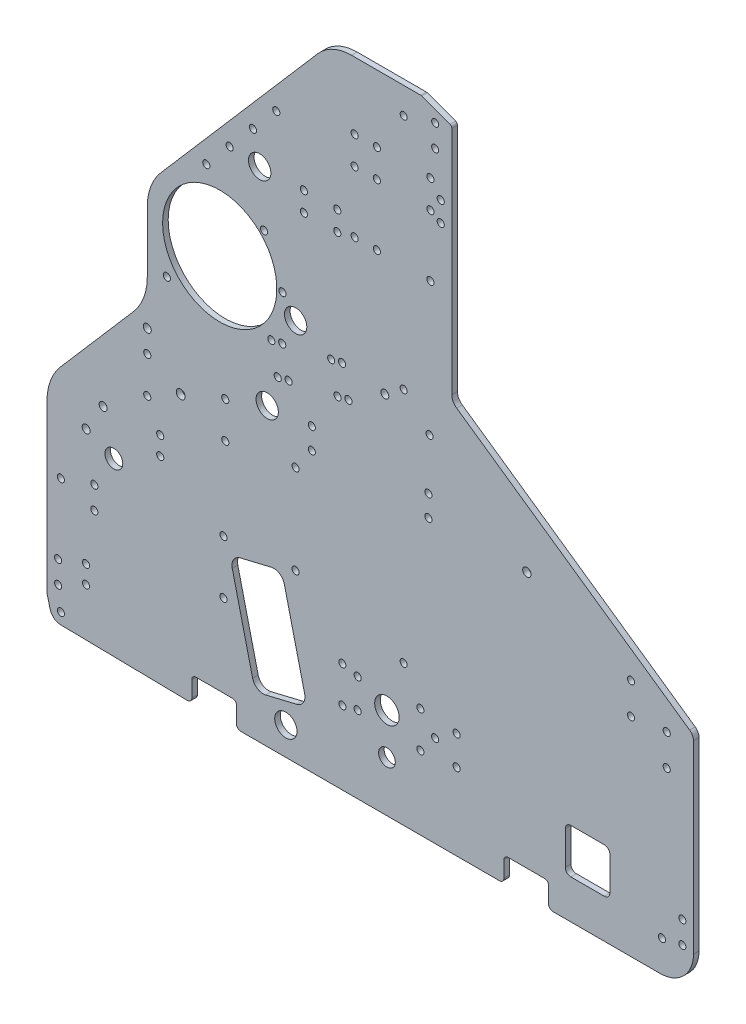
SolidWorks part; units mm, degrees
ref_plane "Front Plane" through (0, 0, 0) normal (0, 0, 1) x (1, 0, 0)
ref_plane "Top Plane" through (0, 0, 0) normal (0, 1, 0) x (1, 0, 0)
ref_plane "Right Plane" through (0, 0, 0) normal (1, 0, 0) x (0, 0, -1)
sketch "Sketch1" plane through (0, 0, 0) normal (0, 0, 1) x (1, 0, 0)
  line L0 (82.55, -20.32) -> (82.55, -6.35)
  line L2 (0, 0) -> (0, 157.48)
  line L4 (368.3, -20.32) -> (368.3, 106.68)
  line L5 (82.55, -6.35) -> (107.95, -6.35)
  line L6 (107.95, -6.35) -> (107.95, -20.32)
  line L7 (107.95, -20.32) -> (260.35, -20.32)
  line L8 (260.35, -20.32) -> (260.35, -6.35)
  line L9 (260.35, -6.35) -> (285.75, -6.35)
  line L10 (285.75, -6.35) -> (285.75, -20.32)
  line L11 (285.75, -20.32) -> (368.3, -20.32)
  line L12 (361.95, 12.7) -> (368.3, 12.7) construction
  line L13 (0, 0) -> (6.35, 0) construction
  line L14 (0.1896, -7.8901) -> (1.7771, -14.2401)
  line L15 (7.8295, -19.0491) -> (82.55, -20.32)
  line L16 (0, 0) -> (0, -6.35)
  line L17 (76.2, 128.905) -> (79.375, 128.905) construction
  line L18 (57.15, 118.5863) -> (101.6, 118.5862) construction
  line L19 (57.15, 118.5863) -> (57.15, 139.2238) construction
  line L20 (101.6, 118.5862) -> (101.6, 139.2237) construction
  line L21 (57.15, 139.2238) -> (101.6, 139.2237) construction
  line L22 (57.15, 118.5863) -> (101.6, 139.2237) construction
  line L23 (101.6, 118.5862) -> (57.15, 139.2238) construction
  line L24 (101.6, 139.2237) -> (125.4682, 147.9111) construction
  line L25 (203.2, 59.805) -> (203.2, 194.805) construction
  line L26 (203.2, 194.805) -> (203.2, 329.805) construction
  line L27 (355.6, 332.105) -> (330.2, 332.105) construction
  line L28 (330.2, 332.105) -> (330.2, 217.805) construction
  line L29 (330.2, 217.805) -> (355.6, 217.805) construction
  line L30 (355.6, 217.805) -> (355.6, 332.105) construction
  line L31 (203.2, 344.805) -> (203.2, 194.805) construction
  line L32 (50.8, 332.105) -> (76.2, 332.105) construction
  line L33 (76.2, 332.105) -> (76.2, 217.805) construction
  line L34 (50.8, 217.805) -> (50.8, 332.105) construction
  line L35 (76.2, 217.805) -> (50.8, 217.805) construction
  line L36 (213.2, 344.805) -> (230.6638, 338.455)
  line L37 (203.2, 344.805) -> (161.925, 344.805)
  line L38 (203.2, 344.805) -> (213.2, 344.805)
  line L39 (348.5362, 344.805) -> (413.4623, 344.805)
  line L40 (348.5362, 344.805) -> (230.6638, 344.805) construction
  line L42 (161.925, 344.805) -> (0, 157.48)
  line L44 (230.6638, 338.455) -> (230.6638, 202.565)
  line L45 (230.6638, 202.565) -> (368.3, 106.68)
  line L46 (213.2, 344.805) -> (-141.0713, 344.805) construction
  line L47 (350.3395, -2.3595) -> (368.3, -20.32) construction
  circle A0 centre (6.35, 0) radius 2.032
  circle A1 centre (6.35, 12.7) radius 2.032
  circle A2 centre (361.95, 0) radius 2.032
  circle A3 centre (361.95, 12.7) radius 2.032
  arc A5 (1.7771, -14.2401) -> (7.8295, -19.0491) centre (7.9375, -12.7) ccw
  circle A6 centre (7.9375, -12.7) radius 2.032
  arc A7 (0, -6.35) -> (0.1896, -7.8901) centre (6.35, -6.35) ccw
  circle A8 centre (38.1, 78.105) radius 5.08
  circle A9 centre (76.2, 128.905) radius 2.54
  circle A10 centre (101.6, 118.5862) radius 2.032
  circle A11 centre (101.6, 139.2237) radius 2.032
  circle A12 centre (57.15, 139.2238) radius 2.032
  circle A13 centre (57.15, 118.5863) radius 2.032
  circle A15 centre (203.2, 59.805) radius 2
  circle A16 centre (203.2, 194.805) radius 2
  circle A17 centre (203.2, 329.805) radius 2
  circle A18 centre (63.5, 313.055) radius 2.032
  circle A20 centre (355.6, 332.105) radius 2.032
  circle A21 centre (330.2, 332.105) radius 2.032
  circle A22 centre (355.6, 217.805) radius 2.032
  circle A23 centre (330.2, 217.805) radius 2.032
  circle A24 centre (50.8, 332.105) radius 2.032
  circle A25 centre (76.2, 332.105) radius 2.032
  circle A26 centre (50.8, 217.805) radius 2.032
  circle A27 centre (76.2, 217.805) radius 2.032
  circle A28 centre (221.1381, 335.28) radius 2
  circle A29 centre (224.3138, 298.831) radius 2.032
  circle A30 centre (353.06, 100.7351) radius 2.032
  circle A31 centre (332.74, 115.9751) radius 2.032
  circle A32 centre (332.74, 98.1951) radius 2.032
  circle A33 centre (353.06, 82.9551) radius 2.032
  circle A34 centre (117.3562, 280.4276) radius 2.032
  circle A35 centre (104.0678, 265.0548) radius 2.032
  circle A36 centre (90.7795, 249.682) radius 2.032
  circle A38 centre (130.6445, 295.8004) radius 2.032
  circle A39 centre (68.326, 182.9237) radius 2.032
  circle A40 centre (224.3138, 287.401) radius 2.032
  circle A41 centre (125.4682, 147.9111) radius 6.35
  circle A42 centre (221.1381, 322.58) radius 2
  circle A43 centre (350.3395, -2.3595) radius 2.032
  point P82 (203.2, 344.805)
  point P90 (368.3, 62.484)
  dimension "D6" = 4.064
  dimension "D10" = 6.35
  dimension "D11" = 4.064
  dimension "D17" = 38.1
  dimension "D27" = 4
  dimension "D31" = 4.064
  dimension "D32" = 41.275
  dimension "D36" = 4.064
  dimension "D47" = 39.624
  dimension "D48" = 4.064
  dimension "D25" = 5.08
  dimension "D26" = 4.064
  dimension "D52" = 4.064
  dimension "D65" = 4.064
  dimension "D69" = 10.16
  dimension "D72" = 12.7
  dimension "D2" = 127
  dimension "D3" = 13.97
  dimension "D4" = 25.4
  dimension "D5" = 152.4
  dimension "D7" = 12.7
  dimension "D8" = 6.35
  dimension "D9" = 20.32
  dimension "D12" = 12.7
  dimension "D13" = 1.5875
  dimension "D14" = 82.55
  dimension "D15" = 368.3
  dimension "D16" = 6.35
  dimension "D18" = 98.425
  dimension "D19" = 38.1
  dimension "D20" = 50.8
  dimension "D21" = 3.175
  dimension "D22" = 270
  dimension "D23" = 20.6375
  dimension "D24" = 44.45
  dimension "D28" = 135
  dimension "D29" = 12.7
  dimension "D30" = 15
  dimension "D33" = 63.5
  dimension "D34" = 27.4638
  dimension "D35" = 12.7
  dimension "D37" = 114.3
  dimension "D38" = 25.4
  dimension "D39" = 12.7
  dimension "D40" = 157.48
  dimension "D41" = 142.24
  dimension "D42" = 365.125
  dimension "D43" = 10
  dimension "D44" = 6.35
  dimension "D45" = 31.75
  dimension "D46" = 3.175
  dimension "D49" = 6.35
  dimension "D50" = 203.2
  dimension "D51" = 15.24
  dimension "D53" = 17.78
  dimension "D54" = 17.78
  dimension "D55" = 20.32
  dimension "D56" = 15.24
  dimension "D57" = 92.202
  dimension "D58" = 8.382
  dimension "D59" = 20.32
  dimension "D60" = 20.32
  dimension "D61" = 8.382
  dimension "D62" = 20.32
  dimension "D63" = 8.382
  dimension "D64" = 8.382
  dimension "D66" = 35.052
  dimension "D67" = 68.326
  dimension "D68" = 11.43
  dimension "D70" = 25.4
  dimension "D71" = 110
  dimension "D73" = 17.9381
  dimension "D74" = 12.7
  dimension "D75" = 45
  dimension "D76" = 25.4
extrude "Boss-Extrude1" add sketch "Sketch1" along normal blind 3.175 contours L16 A7 L14 A5 L15 L2 A0 A1 A6 region at (171.4792, 119.5149, 0)
fillet "Fillet1" radius 2.286 4 edges at (285.75, -6.35, 1.5875) (107.95, -6.35, 1.5875) (260.35, -6.35, 1.5875) (82.55, -6.35, 1.5875)
fillet "Fillet2" radius 6.35 1 edges at (230.6638, 202.565, 1.5875)
sketch "Sketch2" plane through (0, 0, 0) normal (0, 0, -1) x (-1, 0, 0)
  circle A0 centre (-100.5528, 71.086) radius 2.032 construction
  circle A1 centre (-100.5528, 40.606) radius 2.032 construction
  circle A2 centre (-22.225, 18.2025) radius 2.032 construction
  circle A3 centre (-22.225, 8.0425) radius 2.032 construction
  circle A4 centre (-100.5528, 71.086) radius 2.032
  circle A5 centre (-100.5528, 40.606) radius 2.032
  circle A6 centre (-22.225, 18.2025) radius 2.032
  circle A7 centre (-22.225, 8.0425) radius 2.032
extrude "Cut-Extrude1" cut sketch "Sketch2" against normal through all
fillet "Fillet3" radius 1.5875 2 edges at (230.6638, 338.455, 1.5875) (213.2, 344.805, 1.5875)
sketch "Sketch3" plane through (0, 0, 3.175) normal (0, 0, 1) x (1, 0, 0)
  line L0 (132.9524, 63.2646) -> (132.7215, 64.2281) construction
  line L1 (128.3814, 66.8897) -> (110.6828, 62.6472) construction
  line L2 (114.5132, 58.4237) -> (126.8822, 61.3887) construction
  line L3 (108.0212, 58.3071) -> (108.2522, 57.3436) construction
  line L4 (131.2006, 57.703) -> (140.0164, 20.9265) construction
  line L5 (144.0993, 16.7636) -> (132.9524, 63.2646) construction
  line L6 (108.2522, 57.3436) -> (119.3991, 10.8426) construction
  line L7 (121.1509, 16.4042) -> (112.3351, 53.1807) construction
  line L8 (119.3991, 10.8426) -> (119.6301, 9.8791) construction
  line L9 (144.3303, 15.8001) -> (144.0993, 16.7636) construction
  line L10 (137.8383, 15.6835) -> (125.4694, 12.7185) construction
  line L11 (123.9701, 7.2175) -> (141.6687, 11.4601) construction
  line L12 (132.9524, 63.2646) -> (132.7215, 64.2281)
  line L13 (128.3814, 66.8897) -> (110.6828, 62.6472)
  line L14 (114.5132, 58.4237) -> (126.8822, 61.3887)
  line L15 (108.0212, 58.3071) -> (108.2522, 57.3436)
  line L16 (131.2006, 57.703) -> (140.0164, 20.9265)
  line L17 (144.0993, 16.7636) -> (132.9524, 63.2646)
  line L18 (108.2522, 57.3436) -> (119.3991, 10.8426)
  line L19 (121.1509, 16.4042) -> (112.3351, 53.1807)
  line L20 (119.3991, 10.8426) -> (119.6301, 9.8791)
  line L21 (144.3303, 15.8001) -> (144.0993, 16.7636)
  line L22 (137.8383, 15.6835) -> (125.4694, 12.7185)
  line L23 (123.9701, 7.2175) -> (141.6687, 11.4601)
  line L24 (127.7894, 69.3598) -> (110.0908, 65.1172)
  line L25 (105.5512, 57.715) -> (105.7822, 56.7515)
  line L26 (105.7822, 56.7515) -> (116.9291, 10.2505)
  line L27 (116.9291, 10.2505) -> (117.16, 9.287)
  line L28 (124.5622, 4.7475) -> (142.2608, 8.99)
  line L29 (146.8003, 16.3922) -> (146.5694, 17.3557)
  line L30 (146.5694, 17.3557) -> (135.4225, 63.8567)
  line L31 (135.4225, 63.8567) -> (135.1915, 64.8202)
  line L32 (14.605, -0.1369) -> (103.7278, 32.3011) construction
  line L33 (14.605, -0.1369) -> (103.7278, 32.3011)
  line L34 (0, -6.35) -> (0, 157.48) construction
  line L35 (-39.6666, 74.7152) -> (103.7278, 126.9065) construction
  line L36 (26.9875, 46.9531) -> (26.9875, 59.6531) construction
  line L37 (107.95, -20.32) -> (260.35, -20.32) construction
  line L38 (64.5259, 92.5258) -> (64.5259, 102.9405) construction
  line L39 (131.6538, 14.201) -> (136.0946, -4.3242) construction
  arc A0 (132.7215, 64.2281) -> (128.6308, 66.9403) centre (129.2206, 63.3889) ccw construction
  arc A1 (110.6828, 62.6472) -> (110.4377, 62.5791) centre (111.522, 59.1463) ccw construction
  arc A2 (128.6308, 66.9403) -> (128.3814, 66.8897) centre (129.2206, 63.3889) ccw construction
  arc A3 (110.4377, 62.5791) -> (108.0212, 58.3071) centre (111.522, 59.1463) ccw construction
  arc A4 (119.6301, 9.8791) -> (123.7207, 7.1669) centre (123.1309, 10.7183) ccw construction
  arc A5 (141.9139, 11.5281) -> (144.3303, 15.8001) centre (140.8295, 14.9609) ccw construction
  arc A6 (141.6687, 11.4601) -> (141.9139, 11.5281) centre (140.8295, 14.9609) ccw construction
  arc A7 (123.7207, 7.1669) -> (123.9701, 7.2175) centre (123.1309, 10.7183) ccw construction
  arc A8 (132.7215, 64.2281) -> (128.6308, 66.9403) centre (129.2206, 63.3889) ccw
  arc A9 (110.6828, 62.6472) -> (110.4377, 62.5791) centre (111.522, 59.1463) ccw
  arc A10 (128.6308, 66.9403) -> (128.3814, 66.8897) centre (129.2206, 63.3889) ccw
  arc A11 (110.4377, 62.5791) -> (108.0212, 58.3071) centre (111.522, 59.1463) ccw
  arc A12 (119.6301, 9.8791) -> (123.7207, 7.1669) centre (123.1309, 10.7183) ccw
  arc A13 (141.9139, 11.5281) -> (144.3303, 15.8001) centre (140.8295, 14.9609) ccw
  arc A14 (141.6687, 11.4601) -> (141.9139, 11.5281) centre (140.8295, 14.9609) ccw
  arc A15 (123.7207, 7.1669) -> (123.9701, 7.2175) centre (123.1309, 10.7183) ccw
  arc A16 (110.0908, 65.1172) -> (109.6726, 65.0012) centre (111.522, 59.1463) ccw
  arc A17 (109.6726, 65.0012) -> (105.5512, 57.715) centre (111.522, 59.1463) ccw
  arc A18 (117.16, 9.287) -> (124.1369, 4.6613) centre (123.1309, 10.7183) ccw
  arc A19 (124.1369, 4.6613) -> (124.5622, 4.7475) centre (123.1309, 10.7183) ccw
  arc A20 (142.2608, 8.99) -> (142.6789, 9.1061) centre (140.8295, 14.9609) ccw
  arc A21 (142.6789, 9.1061) -> (146.8003, 16.3922) centre (140.8295, 14.9609) ccw
  arc A22 (135.1915, 64.8202) -> (128.2147, 69.446) centre (129.2206, 63.3889) ccw
  arc A23 (128.2147, 69.446) -> (127.7894, 69.3598) centre (129.2206, 63.3889) ccw
  circle A24 centre (136.0946, -4.3242) radius 6.35
  circle A26 centre (134.1438, 208.2281) radius 2.032 construction
  circle A33 centre (26.9875, 46.9531) radius 2.032
  circle A34 centre (26.9875, 59.6531) radius 2.032
  circle A35 centre (7.9375, 53.3031) radius 2.032
  circle A37 centre (32.0306, 100.8109) radius 32.385 construction
  circle A38 centre (32.0306, 100.8109) radius 2.286
  circle A39 centre (123.682, 233.4851) radius 2.032 construction
  circle A40 centre (64.5259, 102.9405) radius 2.032
  circle A41 centre (64.5259, 92.5258) radius 2.032
  circle A42 centre (134.1438, 208.2281) radius 2.032
  circle A43 centre (123.682, 233.4851) radius 2.032
  ellipse E0 centre (124.5974, 48.8487) end of major axis (128.5376, 61.3578) minor radius 6 (131.2006, 57.703) -> (126.8822, 61.3887) ccw construction
  ellipse E1 centre (122.2349, 48.2824) end of major axis (113.0518, 57.6456) minor radius 6 (114.5132, 58.4237) -> (112.3351, 53.1807) ccw construction
  ellipse E2 centre (127.7541, 25.2585) end of major axis (131.6942, 37.7675) minor radius 6 (121.1509, 16.4042) -> (125.4694, 12.7185) ccw construction
  ellipse E3 centre (130.1166, 25.8248) end of major axis (139.2998, 16.4616) minor radius 6 (137.8383, 15.6835) -> (140.0164, 20.9265) ccw construction
  ellipse E4 centre (124.5974, 48.8487) end of major axis (128.5376, 61.3578) minor radius 6 (131.2006, 57.703) -> (126.8822, 61.3887) ccw
  ellipse E5 centre (122.2349, 48.2824) end of major axis (131.4181, 38.9192) minor radius 6 (114.5132, 58.4237) -> (112.3351, 53.1807) ccw
  ellipse E6 centre (127.7541, 25.2585) end of major axis (123.8139, 12.7495) minor radius 6 (121.1509, 16.4042) -> (125.4694, 12.7185) ccw
  ellipse E7 centre (130.1166, 25.8248) end of major axis (139.2998, 16.4616) minor radius 6 (137.8383, 15.6835) -> (140.0164, 20.9265) ccw
  point P93 (26.9875, 53.3031)
  point P115 (32.0306, 100.8109)
  dimension "D3" = 64.77
  dimension "D4" = 4.572
  dimension "D8" = 4.064
  dimension "D13" = 12.7
  dimension "D2" = 88.9
  dimension "D5" = 7.9375
  dimension "D6" = 19.05
  dimension "D7" = 73.6231
  dimension "D9" = 12.7
  dimension "D10" = 10.4147
  dimension "D11" = 37.5384
  dimension "D12" = 45.5727
  dimension "D14" = 19.05
  dimension "D1" = 2.54
extrude "Cut-Extrude2" cut sketch "Sketch3" against normal through all contours A22 A23 L24 A16 A17 L25 L26 L27 A18 A19 L28 A20 A21 L29 L30 L31 A15 A12 L20 L18 L15 A11 A9 L13 A10 A8 L12 L17 L21 A13 A14 L23 | A12 A15 L23 A14 A13 L21 L17 L12 A8 A10 L13 A9 A11 L15 L18 L20 E7 L22 E6 L19 E5 L14 E4 L16 | L22 E7 L16 E4 L14 E5 L19 E6 | A38 | A41 | A40 | A35 | A34 | A33 | A43 | A42 | A24 region at (137.844, 39.8506, 3.175) region at (126.1758, 37.0536, 3.175) region at (128.1544, 68.6507, 3.175) region at (32.0306, 100.8109, 3.175) region at (64.5259, 102.9405, 3.175) region at (64.5259, 92.5258, 3.175)
sketch "Sketch4" plane through (0, 0, 3.175) normal (0, 0, 1) x (1, 0, 0)
  line L0 (57.15, 139.2238) -> (101.6, 139.2237) construction
  line L1 (168.275, 21.4312) -> (212.725, 21.4312) construction
  line L2 (168.275, 21.4312) -> (168.275, 42.0687) construction
  line L3 (168.275, 42.0687) -> (212.725, 42.0687) construction
  line L4 (212.725, 21.4312) -> (212.725, 42.0687) construction
  line L5 (168.275, 21.4312) -> (212.725, 42.0687) construction
  line L6 (168.275, 42.0687) -> (212.725, 21.4312) construction
  line L7 (57.15, 118.5863) -> (57.15, 139.2238) construction
  line L8 (107.95, -20.32) -> (260.35, -20.32) construction
  line L9 (193.675, 31.75) -> (177.005, 31.75) construction
  line L10 (190.5, 31.75) -> (193.675, 31.75) construction
  line L11 (6.35, 12.7) -> (361.95, 12.7) construction
  line L12 (107.95, -6.35) -> (107.95, -20.32) construction
  line L13 (193.675, 31.75) -> (220.6625, 31.75) construction
  line L14 (177.005, 23.4569) -> (177.005, 40.0431) construction
  line L15 (213.2, 44.805) -> (193.2, 44.805) construction
  line L16 (213.2, 44.805) -> (213.2, 344.805) construction
  line L17 (213.2, 344.805) -> (193.2, 344.805) construction
  line L18 (193.2, 44.805) -> (193.2, 344.805) construction
  line L19 (213.2, 44.805) -> (193.2, 344.805) construction
  line L20 (213.2, 344.805) -> (193.2, 44.805) construction
  line L21 (226.1381, 335.28) -> (226.1381, 31.75) construction
  line L22 (237.33, 40.0431) -> (233.3612, 40.0431) construction
  line L23 (237.33, 23.4569) -> (233.3612, 23.4569) construction
  circle A0 centre (168.275, 42.0687) radius 2.032
  circle A1 centre (212.725, 42.0687) radius 2.032
  circle A2 centre (212.725, 21.4312) radius 2.032
  circle A3 centre (168.275, 21.4312) radius 2.032
  circle A4 centre (193.675, 31.75) radius 6.985
  circle A7 centre (220.6625, 31.75) radius 14.2875 construction
  circle A8 centre (193.675, 31.75) radius 12.7 construction
  circle A9 centre (177.005, 40.0431) radius 2.032
  circle A10 centre (177.005, 23.4569) radius 2.032
  circle A11 centre (237.33, 40.0431) radius 2.032 construction
  circle A12 centre (237.33, 23.4569) radius 2.032 construction
  circle A13 centre (193.675, 8.4667) radius 4.7625
  circle A14 centre (221.1381, 31.75) radius 2.032
  circle A15 centre (221.1381, 31.75) radius 5 construction
  circle A16 centre (221.1381, 335.28) radius 5 construction
  circle A17 centre (233.3612, 23.4569) radius 2.032
  circle A18 centre (233.3612, 40.0431) radius 2.032
  point P0 (190.5, 31.75)
  point P26 (203.2, 194.805)
  point P38 (177.005, 31.75)
  dimension "D1" = 4.064
  dimension "D4" = 13.97
  dimension "D7" = 9.525
  dimension "D10" = 25.4
  dimension "D11" = 28.575
  dimension "D16" = 10
  dimension "D17" = 4.064
  dimension "D18" = 10
  dimension "D2" = 52.07
  dimension "D3" = 3.175
  dimension "D5" = 82.55
  dimension "D6" = 26.9875
  dimension "D8" = 20
  dimension "D9" = 300
  dimension "D12" = 16.67
  dimension "D13" = 16.5862
  dimension "D14" = 60.325
  dimension "D15" = 23.2833
  dimension "D19" = 3.9688
extrude "Cut-Extrude3" cut sketch "Sketch4" against normal through all
sketch "Sketch5" plane through (0, 0, 0) normal (0, 0, -1) x (-1, 0, 0)
  line L0 (-57.15, 223.5947) -> (-57.15, 165.3337)
  line L1 (-161.925, 344.805) -> (-52.7201, 218.4699) construction
  line L2 (-57.15, 165.3337) -> (0, 99.219)
  line L3 (0, -6.35) -> (0, 157.48) construction
  line L4 (-147.864, -30.311) -> (-147.864, -16.0874)
  line L5 (-50.4199, 215.8089) -> (0, 157.48) construction
  line L6 (-57.15, 223.5947) -> (0, 157.48)
  line L7 (0, 157.48) -> (0, 99.219)
  line L8 (-98.425, 208.2281) -> (-141.6756, 197.9719) construction
  line L11 (-362.2573, 33.83) -> (-297.0122, 33.83) construction
  line L13 (-273.3975, 139.7291) -> (-362.2573, 33.83) construction
  line L16 (-368.3, -20.32) -> (-368.3, 106.68) construction
  line L19 (-285.75, -20.32) -> (-368.3, -20.32) construction
  circle A0 centre (-98.425, 208.2281) radius 32.5437
  circle A1 centre (-141.6756, 197.9719) radius 6.35
  circle A3 centre (-273.3975, 139.7291) radius 2.39
  circle A5 centre (-362.2573, 33.83) radius 2.667 construction
  dimension "D3" = 65.0875
  dimension "D7" = 12.7
  dimension "D8" = 4.78
  dimension "D1" = 38.1
  dimension "D2" = 57.15
  dimension "D4" = 41.275
  dimension "D5" = 41.275
  dimension "D6" = 138.2414
  dimension "D9" = 22.2382
  dimension "D10" = 50
  dimension "D11" = 11.6447
  dimension "D12" = 94.9025
  dimension "D14" = 62.5
  dimension "D13" = 44.45
  dimension "D15" = 160.0491
extrude "Cut-Extrude5" cut sketch "Sketch5" against normal through all contours A0 | L7 L6 L0 L2 | A3 | A1 region at (28.575, 161.4068, 0) region at (98.425, 208.2281, 0) region at (273.3975, 139.7291, 0)
fillet "Fillet4" radius 31.75 3 edges at (0, 99.219, 1.5875) (57.15, 165.3337, 1.5875) (57.15, 223.5947, 1.5875)
sketch "Sketch6" plane through (0, 0, 3.175) normal (0, 0, 1) x (1, 0, 0)
  line L0 (285.75, -20.32) -> (368.3, -20.32) construction
  line L1 (298.45, 27.305) -> (317.5, 27.305)
  line L2 (295.275, 24.13) -> (295.275, 5.08)
  line L3 (298.45, 1.905) -> (317.5, 1.905)
  line L4 (320.675, 24.13) -> (320.675, 5.08)
  line L5 (295.275, 27.305) -> (320.675, 1.905) construction
  line L6 (295.275, 1.905) -> (320.675, 27.305) construction
  line L7 (368.3, -20.32) -> (368.3, 106.68) construction
  arc A0 (295.275, 5.08) -> (298.45, 1.905) centre (298.45, 5.08) ccw
  arc A1 (317.5, 1.905) -> (320.675, 5.08) centre (317.5, 5.08) ccw
  arc A2 (317.5, 27.305) -> (320.675, 24.13) centre (317.5, 24.13) cw
  arc A3 (298.45, 27.305) -> (295.275, 24.13) centre (298.45, 24.13) ccw
  point P0 (307.975, 14.605)
  dimension "D2" = 3.175
  dimension "D1" = 25.4
  dimension "D3" = 22.225
  dimension "D4" = 47.625
extrude "Cut-Extrude6" cut sketch "Sketch6" against normal through all
fillet "Fillet5" radius 25.4 1 edges at (161.925, 344.805, 1.5875)
sketch "Sketch8" plane through (0, 0, 0) normal (0, 0, -1) x (-1, 0, 0)
  line L0 (-230.6638, 337.343) -> (-230.6638, 205.8802) construction
  line L1 (-230.6638, 255.905) -> (-175.26, 255.905) construction
  line L2 (-175.26, 255.905) -> (-175.26, 306.705) construction
  line L3 (-175.26, 306.705) -> (-230.6638, 306.705) construction
  line L4 (-173.5432, 344.805) -> (-212.9203, 344.805) construction
  line L7 (-107.95, -20.32) -> (-260.35, -20.32) construction
  circle A0 centre (-218.44, 290.83) radius 3.9687
  circle A1 centre (-218.44, 290.83) radius 2.032
  circle A2 centre (218.44, 265.7972) radius 3.9687
  circle A3 centre (218.44, 265.7972) radius 2.032
  circle A4 centre (-205.74, 290.83) radius 3.9687
  circle A5 centre (-205.74, 290.83) radius 2.032
  circle A6 centre (-187.96, 290.83) radius 3.9687
  circle A7 centre (-187.96, 290.83) radius 2.032
  circle A8 centre (-187.96, 306.705) radius 2.032
  circle A9 centre (-175.26, 290.83) radius 3.9687
  circle A10 centre (-175.26, 290.83) radius 2.032
  circle A11 centre (-205.74, 306.705) radius 2.032
  circle A13 centre (-205.74, 255.905) radius 2.032
  circle A14 centre (-187.96, 255.905) radius 2.032
  circle A16 centre (-218.44, 306.705) radius 2.032
  circle A17 centre (-175.26, 306.705) radius 2.032
  circle A18 centre (-175.26, 255.905) radius 2.032
  circle A19 centre (-218.44, 255.905) radius 2.032
  circle A20 centre (-218.44, 306.705) radius 3.9687
  circle A21 centre (-205.74, 306.705) radius 3.9687
  circle A22 centre (-175.26, 306.705) radius 3.9687
  circle A23 centre (-218.44, 255.905) radius 3.9687
  circle A24 centre (-205.74, 255.905) radius 3.9687
  circle A25 centre (-187.96, 255.905) radius 3.9687
  circle A26 centre (-175.26, 255.905) radius 3.9687
  circle A27 centre (-187.96, 306.705) radius 3.9687
  dimension "D1" = 7.9375
  dimension "D7" = 4.064
  dimension "D13" = 12.2237
  dimension "D2" = 12.2237
  dimension "D3" = 12.7
  dimension "D4" = 17.78
  dimension "D5" = 12.7
  dimension "D6" = 88.9
  dimension "D8" = 38.1
  dimension "D9" = 17.78
  dimension "D10" = 12.7
  dimension "D11" = 55.4037
  dimension "D12" = 12.7
  dimension "D14" = 311.15
extrude "Cut-Extrude7" cut sketch "Sketch8" against normal through all contours A16 | A17 | A18 | A19 | A8 | A14 | A1 | A7 | A10 region at (218.44, 306.705, 0) region at (175.26, 306.705, 0) region at (175.26, 255.905, 0) region at (218.44, 255.905, 0)
sketch "Sketch10" plane through (0, 0, 3.175) normal (0, 0, 1) x (1, 0, 0)
  circle A4 centre (141.6425, 74.6844) radius 2.032 construction
  circle A5 centre (141.6425, 125.4844) radius 2.032 construction
  circle A6 centre (141.6425, 74.6844) radius 2.032
  circle A7 centre (141.6425, 125.4844) radius 2.032
extrude "Cut-Extrude8" cut sketch "Sketch10" against normal through all
sketch "Sketch11" plane through (0, 0, 3.175) normal (0, 0, 1) x (1, 0, 0)
  ellipse E4 centre (150.8814, 138.43) end of major axis (150.8814, 140.462) minor radius 2.032
  ellipse E5 centre (150.8814, 150.495) end of major axis (150.8814, 152.527) minor radius 2.032
  ellipse E6 centre (217.3024, 150.495) end of major axis (217.3024, 152.527) minor radius 2.032
  ellipse E7 centre (217.3024, 138.43) end of major axis (217.3024, 140.462) minor radius 2.032
extrude "Cut-Extrude9" cut sketch "Sketch11" against normal through all
sketch "Sketch12" plane through (0, 0, 0) normal (0, 0, -1) x (-1, 0, 0)
  line L0 (-173.5432, 344.805) -> (-212.9203, 344.805) construction
  circle A0 centre (-165.4175, 264.635) radius 2.032
  circle A1 centre (-203.2, 329.805) radius 2 construction
  circle A2 centre (-165.4175, 253.5225) radius 2.032
  circle A3 centre (-146.3675, 253.5225) radius 2.032
  circle A4 centre (-146.3675, 264.635) radius 2.032
  dimension "D1" = 80.17
  dimension "D2" = 4.064
  dimension "D3" = 37.7825
  dimension "D4" = 11.1125
  dimension "D5" = 19.05
extrude "Cut-Extrude10" cut sketch "Sketch12" against normal through all
sketch "Sketch14" plane through (0, 0, 0) normal (0, 0, -1) x (-1, 0, 0)
  line L0 (-130.6445, 295.8004) -> (-121.1847, 263.6885) construction
  line L1 (-121.1847, 263.6885) -> (-90.7795, 249.682) construction
  line L2 (-154.3272, 336.0154) -> (-64.88, 232.5373) construction
  line L4 (-118.517, 269.4796) -> (-115.3937, 261.0208) construction
  line L5 (-118.517, 269.4796) -> (-126.9758, 266.3562) construction
  line L6 (-126.9758, 266.3562) -> (-123.8524, 257.8974) construction
  line L7 (-115.3937, 261.0208) -> (-123.8524, 257.8974) construction
  line L8 (-118.517, 269.4796) -> (-123.8524, 257.8974) construction
  line L9 (-126.9758, 266.3562) -> (-115.3937, 261.0208) construction
  circle A0 centre (-121.1847, 263.6885) radius 6.376
  dimension "D1" = 22.225
  dimension "D2" = 9.017
extrude "Cut-Extrude11" cut sketch "Sketch14" against normal through all
sketch "Sketch15" plane through (0, 0, 3.175) normal (0, 0, 1) x (1, 0, 0)
  line L0 (38.1, 78.105) -> (35.0376, 98.2034) construction
  line L1 (20.5874, 75.6997) -> (81.7263, 75.6997) construction
  line L2 (57.15, 139.2237) -> (57.15, 151.9237) construction
  line L3 (52.4937, 153.9549) -> (22.3594, 84.8727) construction
  line L4 (56.0505, 156.8833) -> (192.439, 187.1199) construction
  line L5 (52.4937, 153.9549) -> (37.8292, 107.1192) construction
  line L6 (20.5874, 75.6997) -> (38.1, 78.105) construction
  line L7 (35.0376, 98.2034) -> (37.8292, 107.1192) construction
  line L8 (20.5874, 75.6997) -> (22.3594, 84.8727) construction
  line L9 (38.1, 78.105) -> (17.7697, 78.105) construction
  line L10 (17.7697, 78.105) -> (21.6586, 86.5998) construction
  line L11 (21.6586, 86.5998) -> (52.4937, 153.9549) construction
  circle A0 centre (20.5874, 75.6997) radius 2.159 construction
  circle A1 centre (20.5874, 75.6997) radius 2.159 construction
  circle A2 centre (57.15, 139.2237) radius 2.032 construction
  circle A3 centre (57.15, 139.2237) radius 2.032 construction
  circle A4 centre (57.15, 151.9237) radius 2.286
  circle A5 centre (192.439, 187.1199) radius 2.286
  circle A6 centre (57.15, 151.9237) radius 5.08 construction
  circle A7 centre (38.1, 78.105) radius 2.159 construction
  circle A8 centre (38.1, 78.105) radius 2.159
  arc A9 (163.8737, 173.6806) -> (164.5125, 170.7993) centre (165.557, 172.5423) ccw construction
  arc A10 (173.4398, 172.7784) -> (172.801, 175.6597) centre (171.7565, 173.9167) ccw construction
  arc A11 (172.801, 175.6597) -> (173.4398, 172.7784) centre (171.7565, 173.9167) ccw construction
  arc A12 (164.5125, 170.7993) -> (163.8737, 173.6806) centre (165.557, 172.5423) ccw construction
  arc A13 (169.1589, 192.0883) -> (169.7976, 189.2071) centre (168.1143, 190.3453) ccw construction
  arc A14 (169.7976, 189.2071) -> (169.1589, 192.0883) centre (168.1143, 190.3453) ccw construction
  arc A15 (160.2316, 190.1092) -> (160.8704, 187.2279) centre (161.9149, 188.9709) ccw construction
  arc A16 (160.8704, 187.2279) -> (160.2316, 190.1092) centre (161.9149, 188.9709) ccw construction
  arc A17 (129.7766, 166.1214) -> (130.4154, 163.2402) centre (131.4599, 164.9832) ccw construction
  arc A18 (139.3426, 165.2193) -> (138.7039, 168.1005) centre (137.6593, 166.3576) ccw construction
  arc A19 (138.7039, 168.1005) -> (139.3426, 165.2193) centre (137.6593, 166.3576) ccw construction
  arc A20 (130.4154, 163.2402) -> (129.7766, 166.1214) centre (131.4599, 164.9832) ccw construction
  arc A21 (135.7005, 181.6479) -> (135.0617, 184.5292) centre (134.0172, 182.7862) ccw construction
  arc A22 (135.0617, 184.5292) -> (135.7005, 181.6479) centre (134.0172, 182.7862) ccw construction
  arc A23 (126.1345, 182.55) -> (126.7732, 179.6688) centre (127.8177, 181.4118) ccw construction
  arc A24 (126.7732, 179.6688) -> (126.1345, 182.55) centre (127.8177, 181.4118) ccw construction
  arc A25 (163.8737, 173.6806) -> (164.5125, 170.7993) centre (165.557, 172.5423) ccw
  arc A26 (173.4398, 172.7784) -> (172.801, 175.6597) centre (171.7565, 173.9167) ccw
  arc A27 (172.801, 175.6597) -> (173.4398, 172.7784) centre (171.7565, 173.9167) ccw
  arc A28 (164.5125, 170.7993) -> (163.8737, 173.6806) centre (165.557, 172.5423) ccw
  arc A29 (169.1589, 192.0883) -> (169.7976, 189.2071) centre (168.1143, 190.3453) ccw
  arc A30 (169.7976, 189.2071) -> (169.1589, 192.0883) centre (168.1143, 190.3453) ccw
  arc A31 (160.2316, 190.1092) -> (160.8704, 187.2279) centre (161.9149, 188.9709) ccw
  arc A32 (160.8704, 187.2279) -> (160.2316, 190.1092) centre (161.9149, 188.9709) ccw
  arc A33 (129.7766, 166.1214) -> (130.4154, 163.2402) centre (131.4599, 164.9832) ccw
  arc A34 (139.3426, 165.2193) -> (138.7039, 168.1005) centre (137.6593, 166.3576) ccw
  arc A35 (138.7039, 168.1005) -> (139.3426, 165.2193) centre (137.6593, 166.3576) ccw
  arc A36 (130.4154, 163.2402) -> (129.7766, 166.1214) centre (131.4599, 164.9832) ccw
  arc A37 (135.7005, 181.6479) -> (135.0617, 184.5292) centre (134.0172, 182.7862) ccw
  arc A38 (135.0617, 184.5292) -> (135.7005, 181.6479) centre (134.0172, 182.7862) ccw
  arc A39 (126.1345, 182.55) -> (126.7732, 179.6688) centre (127.8177, 181.4118) ccw
  arc A40 (126.7732, 179.6688) -> (126.1345, 182.55) centre (127.8177, 181.4118) ccw
  circle A41 centre (22.3594, 84.8727) radius 2.286 construction
  circle A42 centre (22.3594, 84.8727) radius 2.286
  point P39 (52.4937, 153.9549)
  dimension "D2" = 4.572
  dimension "D6" = 10.16
  dimension "D1" = 12.7
  dimension "D3" = 139.7
  dimension "D4" = 12.5
  dimension "D5" = 74.0778
  dimension "D7" = 49.0778
extrude "Cut-Extrude12" cut sketch "Sketch15" against normal through all
sketch "Sketch16" plane through (0, 0, 3.175) normal (0, 0, 1) x (1, 0, 0)
  circle A0 centre (98.425, 208.2281) radius 34.925 construction
  circle A1 centre (98.425, 208.2281) radius 34.925
  circle A2 centre (98.425, 208.2281) radius 36.195
  dimension "D1" = 1.27
fillet "Fillet7" radius 5.08 1 edges at (368.3, 106.68, 1.5875)
fillet "Fillet8" radius 2.54 4 edges at (82.55, -20.32, 1.5875) (107.95, -20.32, 1.5875) (260.35, -20.32, 1.5875) (285.75, -20.32, 1.5875)
sketch "Sketch17" plane through (0, 0, 3.175) normal (0, 0, 1) x (1, 0, 0)
  line L0 (230.6638, 337.343) -> (230.6638, 205.8802) construction
  line L1 (173.5432, 344.805) -> (212.9203, 344.805) construction
  circle A0 centre (217.9638, 179.705) radius 2.032
  dimension "D1" = 12.7
  dimension "D3" = 4.064
  dimension "D2" = 165.1
extrude "Cut-Extrude13" cut sketch "Sketch17" against normal through all contours A0
fillet "Fillet9" radius 19.05 1 edges at (368.3, -20.32, 1.5875)
equation "\"D7@Sketch15\"=\"D5@Sketch15\"-25mm"
